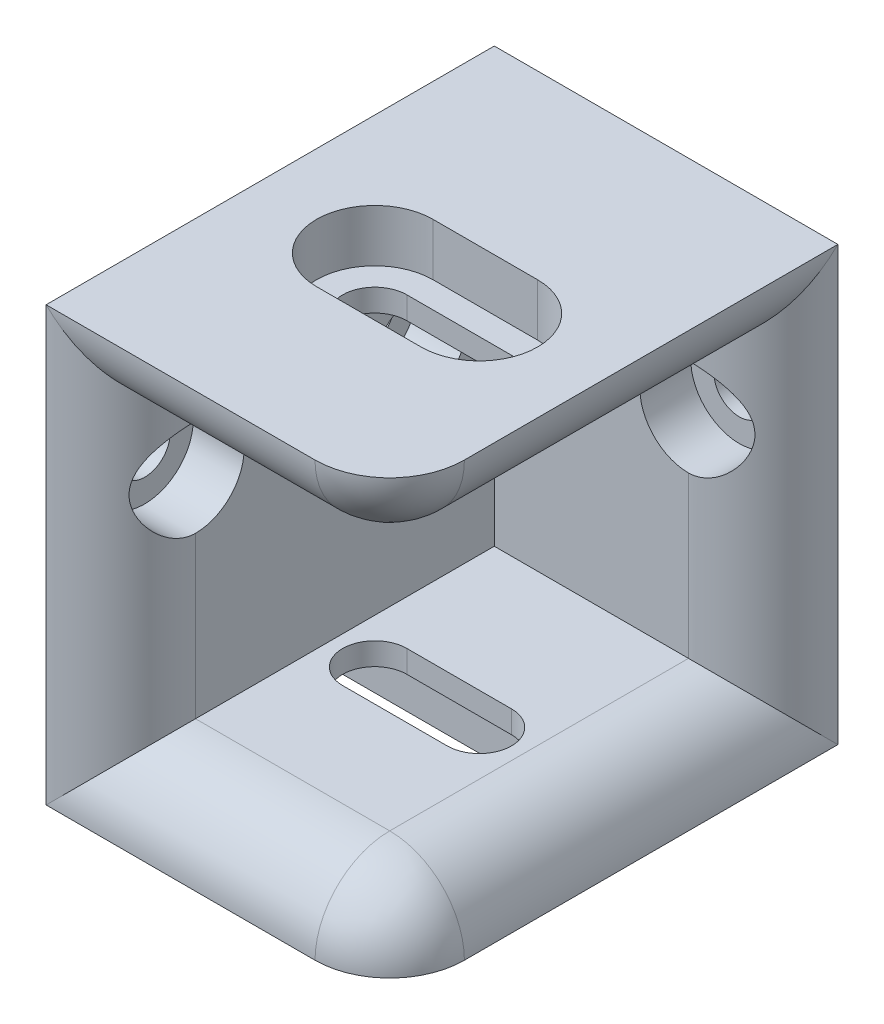
SolidWorks part; units mm, degrees
material "ABS"
ref_plane "Front Plane" through (0, 0, 0) normal (0, 0, 1) x (1, 0, 0)
ref_plane "Top Plane" through (0, 0, 0) normal (0, 1, 0) x (1, 0, 0)
ref_plane "Right Plane" through (0, 0, 0) normal (1, 0, 0) x (0, 0, -1)
sketch "Sketch1" plane through (0, 0, 0) normal (0, 1, 0) x (1, 0, 0)
  line L1 (0, 0) -> (23, 0)
  line L2 (0, 0) -> (0, 30)
  line L3 (0, 30) -> (23, 30)
  line L4 (23, 0) -> (23, 30)
  dimension "D1" = 23
  dimension "D2" = 30
extrude "Boss-Extrude1" add sketch "Sketch1" along normal blind 5
sketch "Sketch22" plane through (0, 5, 0) normal (0, 1, 0) x (1, 0, 0)
  line L0 (0, 0) -> (5, 0)
  line L1 (0, 0) -> (23, 0) construction
  line L2 (23, 30) -> (23, 25)
  line L3 (23, 0) -> (23, 30) construction
  line L4 (5, 0) -> (5, 25)
  line L5 (5, 25) -> (23, 25)
  line L6 (0, 30) -> (23, 30)
  line L7 (0, 30) -> (0, 0)
  dimension "D1" = 5
  dimension "D2" = 5
extrude "Boss-Extrude3" add sketch "Sketch22" along normal blind 24
hole_wizard "CBORE for M3 Hex Socket Head Cap Screw6" positions "Sketch29" profile "Sketch30" counterbore size "M3" standard "ISO" end condition through all
sketch "Sketch29" plane through (0, 0, -25) normal (0, 0, 1) x (1, 0, 0)
  line L2 (23, 29) -> (23, 5) construction
  line L3 (5, 29) -> (23, 29) construction
  point P13 (18, 19)
  dimension "D1" = 10
  dimension "D2" = 5
sketch "Sketch30" plane through (18, 19, -25) normal (1, 0, 0) x (0, -1, 0)
  line L0 (0, 0) -> (0, 5)
  line L1 (0, 5) -> (1.7, 5)
  line L3 (1.7, 5) -> (1.7, 3.4)
  line L4 (1.7, 3.4) -> (3.25, 3.4)
  line L5 (3.25, 3.4) -> (3.25, 0)
  line L7 (3.25, 0) -> (0, 0)
  line L11 (0, -6.35) -> (0, 107.95) construction
  dimension "Thru Hole Dia." = 3.4
  dimension "Thru Hole Depth" = 5
  dimension "C'Bore Dia." = 6.5
  dimension "C'Bore Depth" = 3.4
hole_wizard "CBORE for M3 Hex Socket Head Cap Screw7" positions "Sketch31" profile "Sketch32" counterbore size "M3" standard "ISO" end condition through all
sketch "Sketch31" plane through (5, 0, 0) normal (1, 0, 0) x (0, 0, -1)
  line L0 (0, 29) -> (0, 5) construction
  line L2 (25, 29) -> (25, 5) construction
  line L4 (0, 29) -> (25, 29) construction
  point P0 (5, 19)
  point P2 (20, 19)
  dimension "D1" = 5
  dimension "D2" = 10
  dimension "D3" = 10
  dimension "D4" = 5
sketch "Sketch32" plane through (5, 19, -5) normal (0, 1, 0) x (0, 0, -1)
  line L0 (0, 0) -> (0, 5)
  line L1 (0, 5) -> (1.7, 5)
  line L3 (1.7, 5) -> (1.7, 3.4)
  line L4 (1.7, 3.4) -> (3.25, 3.4)
  line L5 (3.25, 3.4) -> (3.25, 0)
  line L7 (3.25, 0) -> (0, 0)
  line L11 (0, -6.35) -> (0, 107.95) construction
  dimension "Thru Hole Dia." = 3.4
  dimension "Thru Hole Depth" = 5
  dimension "C'Bore Dia." = 6.5
  dimension "C'Bore Depth" = 3.4
sketch "Sketch33" plane through (0, 0, -25) normal (0, 0, 1) x (1, 0, 0)
  line L0 (23, 29) -> (23, 5) construction
  line L1 (5, 29) -> (23, 29)
  line L2 (5, 29) -> (5, 24)
  line L3 (5, 24) -> (23, 24)
  line L4 (23, 29) -> (23, 24)
  dimension "D1" = 5
extrude "Boss-Extrude4" add sketch "Sketch33" along normal up to surface (25 mm away) up to face at (9.3333, 11.3333, 0)
sketch "Sketch41" plane through (0, 29, 0) normal (0, 1, 0) x (1, 0, 0)
  line L1 (15, 11.85) -> (8, 11.85)
  line L2 (15, 11.85) -> (15, 16.15)
  line L3 (15, 16.15) -> (8, 16.15)
  line L4 (8, 11.85) -> (8, 16.15)
  line L5 (15, 11.85) -> (8, 16.15) construction
  line L6 (15, 16.15) -> (8, 11.85) construction
  line L7 (0, 30) -> (0, 0) construction
  line L8 (23, 30) -> (0, 30) construction
  arc A0 (15, 16.15) -> (15, 11.85) centre (15, 14) cw
  arc A1 (8, 11.85) -> (8, 16.15) centre (8, 14) cw
  point P0 (11.5, 14)
  dimension "D1" = 16
  dimension "D2" = 15
  dimension "D3" = 4.3
  dimension "D4" = 7
extrude "Cut-Extrude4" cut sketch "Sketch41" against normal through all contours A1 L4 | L4 L1 L2 L3 | A0 L2 region at (11.5, 29, -14) region at (15.9125, 29, -14) region at (7.0875, 29, -14)
sketch "Sketch42" plane through (0, 29, 0) normal (0, 1, 0) x (1, 0, 0)
  line L9 (8, 10.1) -> (15, 10.1)
  line L10 (15, 17.9) -> (8, 17.9)
  line L11 (8, 10.1) -> (15, 10.1)
  line L12 (15, 17.9) -> (8, 17.9)
  arc A5 (8, 17.9) -> (8, 10.1) centre (8, 14) ccw
  arc A6 (15, 10.1) -> (15, 17.9) centre (15, 14) ccw
  arc A7 (8, 17.9) -> (8, 10.1) centre (8, 14) ccw
  arc A8 (15, 10.1) -> (15, 17.9) centre (15, 14) ccw
  dimension "D1" = 1.75
extrude "Cut-Extrude5" cut sketch "Sketch42" against normal blind 3.5
sketch "Sketch43" plane through (0, 0, 0) normal (0, -1, 0) x (1, 0, 0)
  line L1 (2.25, -10.5) -> (20.75, -10.5)
  line L2 (2.25, -10.5) -> (2.25, -17.5)
  line L3 (2.25, -17.5) -> (20.75, -17.5)
  line L4 (20.75, -10.5) -> (20.75, -17.5)
  line L5 (2.25, -10.5) -> (20.75, -17.5) construction
  line L6 (2.25, -17.5) -> (20.75, -10.5) construction
  line L18 (17.15, -14) -> (5.85, -14) construction
  arc A0 (15, -16.15) -> (15, -11.85) centre (15, -14) ccw construction
  arc A1 (8, -11.85) -> (8, -16.15) centre (8, -14) ccw construction
  point P0 (11.5, -14)
  dimension "D1" = 18.5
  dimension "D2" = 7
extrude "Cut-Extrude7" cut sketch "Sketch43" against normal blind 3.5
ref_plane "Plane2" [suppressed] through (23, 29, 0) normal (0, 0, -1) x (-1, 0, 0)
sketch "Sketch40" [suppressed] plane through (23, 0, 0) normal (1, 0, 0) x (0, 0, -1)
  line L0 (0, 29) -> (30, 29) construction
  line L4 (0, 29) -> (0, 24) construction
  circle A0 centre (5, 25.5) radius 2.5
  dimension "D1" = 5
  dimension "D2" = 3.5
  dimension "D3" = 5
extrude "Cut-Extrude3" [suppressed] cut sketch "Sketch40" against normal blind 5
sketch "Sketch44" [suppressed] plane through (23, 0, 0) normal (1, 0, 0) x (0, 0, -1)
  line L0 (0, 5) -> (0, 0) construction
  line L2 (3.5858, 5) -> (6.4142, 5)
  line L3 (0, 5) -> (25, 5) construction
  circle A0 centre (5, 5.5) radius 1.5
  arc A1 (7, 24) -> (3, 24) centre (5, 25.5) ccw construction
  line M6 (25, 5) -> (0, 5)
  dimension "D3" = 3
  dimension "D1" = 5
  dimension "D2" = 20
extrude "Boss-Extrude5" [suppressed] add sketch "Sketch44" along normal blind 2 contours A0 M6
sketch "Sketch46" [suppressed] plane through (25, 0, 0) normal (1, 0, 0) x (0, 0, -1)
  line L1 (3.5858, 5) -> (2.5858, 5)
  line L2 (6.4142, 5) -> (7.4142, 5)
  line L4 (3.5858, 5) -> (6.4142, 5)
  arc A5 (2.5858, 5) -> (7.4142, 5) centre (5, 5.5) ccw
  dimension "D1" = 1
extrude "Boss-Extrude6" [suppressed] add sketch "Sketch46" along normal blind 1
fillet "Fillet1" radius 5 4 edges at (14, 24, 0) (23, 14.5, -25) (14, 5, 0) (5, 14.5, 0)
ref_plane "Plane1" through (0, 0, 0) normal (0, 0, -1) x (-1, 0, 0)
mirror "Mirror1" [suppressed] about plane through (0, 0, 0) normal (0, 0, -1) of bodies 130 122
delete or keep bodies "Body-Delete/Keep 1" [suppressed] type delete bodies bodies 130
fillet "Fillet2" radius 5 4 edges at (23, 3.5355, -1.4645) (23, 25.4645, -1.4645) (23, 5, -17.5) (23, 24, -17.5)
